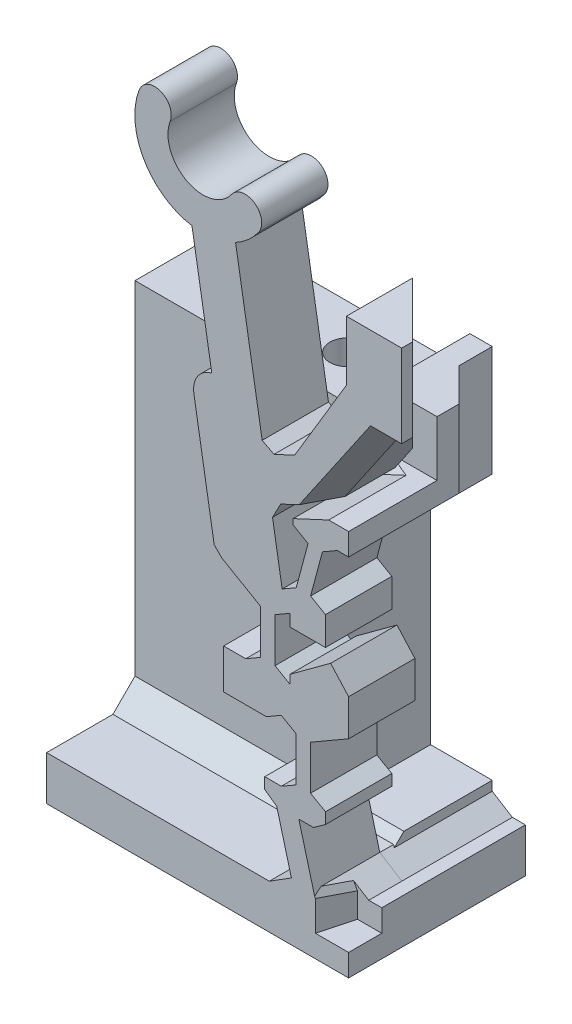
SolidWorks part; units mm, degrees
material "Nylon 6/12"
ref_plane "Front Plane" through (0, 0, 0) normal (0, 0, 1) x (1, 0, 0)
ref_plane "Top Plane" through (0, 0, 0) normal (0, 1, 0) x (1, 0, 0)
ref_plane "Right Plane" through (0, 0, 0) normal (1, 0, 0) x (0, 0, -1)
sketch "Sketch-SkeletonConfigUp" plane through (0, 0, 0) normal (0, 0, 1) x (1, 0, 0)
  line L0 (0, 0) -> (0, -50000) construction
  line L1 (0, 0) -> (4.5811, 6.2164) construction
  line L2 (9.8143, 13.3177) -> (4.5811, 13.945) construction
  line L3 (4.5811, 13.945) -> (2.9713, 10.4094) construction
  line L4 (2.9713, 10.4094) -> (4.5811, 6.2164) construction
  line L5 (4.5811, 13.945) -> (6.2429, 19.1409) construction
  line L6 (2.9713, 10.4094) -> (0.0405, 27.8193) construction
  line L7 (4.5811, 6.2164) -> (9.8143, 13.3177) construction
  line L8 (-587.3593, -797.0242) -> (9.8143, 13.3177) construction
  dimension "D2" = 7.7221
  dimension "D3" = 8.8212
  dimension "D4" = 5.2707
  dimension "D5" = 119.553
  dimension "D6" = 3.8848
  dimension "D7" = 5.4552
  dimension "D8" = 17.6549
  dimension "D9" = 4.4914
  dimension "D10" = 6.745
  dimension "D11" = 145.964
  dimension "D12" = 143.612
sketch "Sketch-SkeletonConfigDown" plane through (0, 0, 0) normal (0, 0, 1) x (1, 0, 0)
  line L0 (0, 0) -> (0, -50000) construction
  line L1 (0, 0) -> (4.5811, 6.2164) construction
  line L2 (9.8143, 13.3177) -> (4.5811, 13.945) construction
  line L3 (4.5811, 13.945) -> (6.1909, 10.4094) construction
  line L4 (6.1909, 10.4094) -> (4.5811, 6.2164) construction
  line L5 (4.5811, 13.945) -> (1.753, 18.6098) construction
  line L6 (6.1909, 10.4094) -> (-8.8652, 19.6294) construction
  line L7 (4.5811, 6.2164) -> (9.8143, 13.3177) construction
  line L8 (-589.9357, -800.5203) -> (9.8143, 13.3177) construction
  dimension "D2" = 7.7221
  dimension "D3" = 8.8212
  dimension "D4" = 5.2707
  dimension "D5" = 119.553
  dimension "D6" = 3.8848
  dimension "D7" = 5.4552
  dimension "D8" = 17.6549
  dimension "D9" = 4.4914
  dimension "D10" = 6.745
  dimension "D11" = 145.964
  dimension "D1" = 143.612
ref_plane "Plane-Cam Base" through (9.128, 0, 0) normal (1, 0, 0) x (0, 0, -1)
ref_plane "Plane-Down-to-Up Derailleur Clearance" through (6.628, 0, 0) normal (1, 0, 0) x (0, 0, -1)
ref_plane "Plane-Cam Cavity Roof" through (5.128, 0, 0) normal (1, 0, 0) x (0, 0, -1)
sketch "Sketch-SwitchBossUp" plane through (0, 0, 0) normal (0, 0, 1) x (1, 0, 0)
  line L0 (3.5811, 11.4759) -> (3.5811, 12.945) construction
  line L2 (6.528, 22.0186) -> (6.528, 24.7229)
  line L3 (6.528, 24.7229) -> (9.028, 24.7229)
  line L5 (5.5811, 12.5552) -> (5.5811, 11.263)
  line L7 (1.5115, 25.1048) -> (2.7157, 17.9518)
  line L8 (-0.4607, 24.7728) -> (0.4359, 19.4465)
  line L9 (2.9713, 10.4094) -> (0.0405, 27.8193) construction
  line L11 (-0.0396, 22.2712) -> (1.9326, 22.6032) construction
  line L15 (6.628, -23.7286) -> (6.628, 23.7286) construction
  line L16 (2.9713, 10.4094) -> (4.5811, 6.2164) construction
  line L17 (3.5811, 12.945) -> (3.5811, 14.945) construction
  line L18 (5.5811, 12.945) -> (5.5811, 14.945) construction
  line L19 (4.2561, 13.945) -> (4.9061, 13.945) construction
  line L20 (3.5811, 14.945) -> (5.5811, 14.945) construction
  line L21 (3.5811, 12.945) -> (5.5811, 12.945) construction
  line L22 (4.5811, 12.945) -> (4.5811, 14.945) construction
  line L23 (4.5811, 6.2164) -> (8.5405, 7.1023) construction
  line L24 (1.9713, 9.4094) -> (1.9713, 11.4094) construction
  line L25 (3.9713, 9.4094) -> (3.9713, 11.4094) construction
  line L26 (3.9713, 9.4094) -> (1.9713, 9.4094) construction
  line L27 (1.9713, 11.4094) -> (3.9713, 11.4094) construction
  line L28 (3.5811, 7.2164) -> (5.5811, 7.2164) construction
  line L29 (3.5811, 7.2164) -> (3.5811, 5.2164) construction
  line L30 (5.5811, 7.2164) -> (5.5811, 5.2164) construction
  line L31 (3.5811, 5.2164) -> (5.5811, 5.2164) construction
  line L32 (4.9061, 6.2164) -> (4.2561, 6.2164) construction
  line L40 (3.2963, 10.4094) -> (2.6463, 10.4094) construction
  line L43 (2.874, 4.5093) -> (0.7934, 4.5093) construction
  line L66 (0.0405, 27.8193) -> (0.0405, 50027.8193) construction
  line L74 (0.5455, 12.7717) -> (-0.3728, 18.2264)
  line L75 (0.3841, 13.7302) -> (2.3564, 14.0622) construction
  line L76 (5.5811, 11.263) -> (5.5811, 12.5552) construction
  line L77 (5.5811, 7.6061) -> (6.628, 8.2105)
  line L80 (5.8152, 10.763) -> (6.628, 9.8603)
  line L81 (9.128, 1033.2419) -> (9.128, 20.0586) construction
  line L82 (2.7987, 17.4587) -> (3.5585, 12.945) construction
  line L83 (3.6203, 12.5779) -> (3.184, 15.1695)
  line L85 (6.9307, 9.5241) -> (8.5405, 7.7363) construction
  line L88 (5.7256, 16.3347) -> (6.8573, 16.3347)
  line L92 (3.7762, 8.3129) -> (6.9307, 9.5241) construction
  line L95 (2.7987, 17.4587) -> (3.101, 15.6625) construction
  line L96 (2.7124, 17.9713) -> (9.128, 19.0513) construction
  line L97 (2.7124, 17.9713) -> (1.7262, 17.8053) construction
  line L98 (1.9713, 9.0197) -> (0.9713, 9.0197)
  line L99 (0.9713, 9.0197) -> (0.9713, 7.2164)
  line L100 (0.9713, 7.2164) -> (2.9061, 7.2164)
  line L101 (4.5811, 6.2164) -> (6.9307, 9.5241) construction
  line L103 (0.0405, 27.8193) -> (1.9448, 26.4638) construction
  line L104 (6.9307, 9.5241) -> (8.5405, 7.7363) construction
  line L106 (13.4904, 14.945) -> (5.5811, 14.945) construction
  line L107 (1.9713, 9.4094) -> (1.9713, 9.0197) construction
  line L109 (0.0405, 27.8193) -> (-2.1498, 28.6358) construction
  line L111 (6.628, 9.8603) -> (6.628, 8.2105)
  line L112 (6.628, 9.8603) -> (6.9307, 9.5241) construction
  line L113 (2.8311, 4.8267) -> (2.8311, 4.3267)
  line L114 (7.3693, 7.7363) -> (7.3563, 7.7363) construction
  line L115 (6.8573, 16.3347) -> (13.4904, 16.3347)
  line L116 (13.4904, 16.3347) -> (13.4904, -1.1653)
  line L117 (13.4904, -1.1653) -> (5.0383, -1.1653)
  line L119 (10.4375, 14.0252) -> (10.4375, 2.1465)
  line L121 (5.0383, -1.1653) -> (5.0383, 1.4614) construction
  line L122 (8.237, 12.8031) -> (10.8637, 12.8031) construction
  line L123 (10.8637, 12.8031) -> (13.4904, 12.8031) construction
  line L124 (10.4375, 2.1465) -> (9.128, 0.837)
  line L125 (8.5892, 7.5847) -> (13.4904, 7.5847) construction
  line L127 (5.5811, 15.3347) -> (5.5811, 14.945) construction
  line L130 (6.0388, 0.837) -> (9.128, 0.837)
  line L132 (2.8311, 4.3267) -> (3.3749, 3.937)
  line L133 (2.9713, 10.4094) -> (6.1909, 10.4094) construction
  line L134 (4.5811, 10.4094) -> (4.5811, 13.945) construction
  line L135 (4.5811, 10.4094) -> (4.5811, 6.2164) construction
  line L136 (0.8973, 12.4192) -> (0.5455, 12.7717)
  line L137 (3.9713, 9.4094) -> (5.5811, 7.2164) construction
  line L139 (5.8152, 10.763) -> (3.9713, 9.4094)
  line L141 (4.0386, 1.4604) -> (3.0388, 0.8347)
  line L142 (3.0388, 0.8347) -> (3.0388, -1.1653)
  line L143 (9.128, 20.0586) -> (9.128, 19.0513) construction
  line L145 (9.128, 18.4729) -> (9.128, -49992.4167) construction
  line L147 (5.5811, 11.263) -> (5.5811, 12.5552) construction
  line L150 (3.0388, -1.1653) -> (5.0383, -1.1653)
  line L151 (3.3749, 3.937) -> (4.3749, 3.937) construction
  line L152 (4.792, 14.945) -> (4.2561, 12.945)
  line L153 (5.442, 14.945) -> (4.9061, 12.945)
  line L157 (3.5811, 16.3347) -> (3.5811, 15.3347) construction
  line L158 (6.117, 15.3347) -> (9.128, 15.3347)
  line L162 (3.2963, 11.4094) -> (3.2963, 9.4094)
  line L164 (2.6463, 11.4094) -> (2.6463, 9.4094)
  line L169 (4.2561, 7.2164) -> (4.2561, 5.2164)
  line L170 (4.9061, 5.2164) -> (4.9061, 7.2164)
  line L175 (4.2561, 7.2164) -> (3.5811, 7.6061)
  line L176 (4.9061, 7.2164) -> (5.5811, 7.6061)
  line L177 (5.5811, 7.2164) -> (5.5811, 7.6061) construction
  line L179 (4.2561, 5.2164) -> (3.5811, 4.8267)
  line L180 (3.5811, 5.2164) -> (3.5811, 4.8267) construction
  line L181 (3.5811, 4.8267) -> (2.8311, 4.8267)
  line L183 (4.9061, 5.2164) -> (5.5811, 4.8267)
  line L184 (5.5811, 5.2164) -> (5.5811, 4.8267) construction
  line L186 (9.128, -23.7286) -> (9.128, 23.7286) construction
  line L187 (2.6463, 9.4094) -> (1.9713, 9.0197)
  line L188 (3.2963, 9.4094) -> (3.9713, 9.0197)
  line L189 (3.2963, 11.4094) -> (3.9713, 11.7991)
  line L190 (2.6463, 11.4094) -> (0.8973, 12.4192)
  line L191 (3.9713, 11.4094) -> (3.9713, 11.7991) construction
  line L192 (3.9713, 11.7991) -> (3.9713, 11.263)
  line L193 (4.9061, 12.945) -> (5.5811, 12.5552)
  line L194 (4.2561, 12.945) -> (3.6203, 12.5779)
  line L195 (3.9713, 11.263) -> (5.5811, 11.263)
  line L196 (3.9713, 9.4094) -> (3.9713, 9.0197)
  line L197 (3.5811, 7.2164) -> (3.5811, 7.6061) construction
  line L199 (3.5811, 7.6061) -> (2.9061, 7.2164)
  line L201 (2.8311, 4.3267) -> (2.8311, 3.937) construction
  line L202 (2.8311, 3.937) -> (3.3749, 3.937) construction
  line L203 (10.4375, 14.0252) -> (9.128, 15.3347)
  line L204 (5.0383, 1.437) -> (3.0388, 1.437) construction
  line L205 (3.0388, 1.437) -> (3.0388, 0.8347) construction
  line L206 (5.0383, 1.4614) -> (6.0388, 0.837)
  line L207 (9.128, 19.0513) -> (9.128, 18.4729) construction
  line L208 (6.628, 17.3072) -> (9.128, 18.4729) construction
  line L209 (9.128, 20.0586) -> (9.128, 18.4729) construction
  line L210 (6.528, 22.0186) -> (4.1882, 18.1066)
  line L211 (5.0383, 1.4614) -> (4.3749, 3.937)
  line L212 (4.0386, 1.4604) -> (3.3749, 3.937)
  line L214 (4.792, 14.945) -> (4.1169, 15.3347)
  line L215 (4.1169, 15.3347) -> (3.5811, 15.3347) construction
  line L216 (5.442, 14.945) -> (6.117, 15.3347)
  line L217 (5.5811, 12.945) -> (5.5811, 12.5552) construction
  line L218 (5.442, 14.945) -> (5.442, 15.3347) construction
  line L219 (6.117, 15.3347) -> (4.1169, 15.3347) construction
  line L221 (9.028, 20.9729) -> (9.028, 24.7229)
  line L223 (4.1169, 15.5846) -> (5.7256, 16.3347)
  line L224 (3.5811, 16.3347) -> (5.7256, 16.3347) construction
  line L225 (3.5542, 15.8738) -> (5.7256, 16.8864)
  line L226 (4.1169, 15.3347) -> (4.1169, 15.5846)
  line L227 (3.5811, 15.3347) -> (4.1169, 15.5846) construction
  line L228 (4.1882, 18.1066) -> (3.2518, 17.67)
  line L229 (9.028, 20.9729) -> (8.528, 20.9729)
  line L230 (8.528, 20.9729) -> (5.7256, 16.8864)
  line L232 (7.5371, 18.7835) -> (9.128, 21.1198) construction
  line L233 (9.128, 21.1198) -> (9.028, 20.9729) construction
  line L234 (6.628, 17.3072) -> (7.5371, 18.7835) construction
  line L236 (5.7256, 16.8864) -> (6.628, 17.3072) construction
  line L237 (3.184, 15.1695) -> (3.5542, 15.8738)
  line L238 (3.2518, 17.67) -> (2.7157, 17.9518)
  line L239 (5.5811, 4.8267) -> (5.5811, 4.3267)
  line L240 (4.3749, 3.937) -> (5.0373, 3.937)
  line L241 (5.0373, 3.937) -> (5.5811, 4.3267)
  arc A0 (1.5115, 25.1048) -> (2.5558, 26.0289) centre (0.0405, 27.8193) ccw
  arc A1 (-0.4607, 24.7728) -> (-2.8525, 28.8978) centre (0.0405, 27.8193) cw
  arc A2 (-2.8525, 28.8978) -> (-1.447, 28.3738) centre (-2.1498, 28.6358) cw
  arc A3 (2.5558, 26.0289) -> (1.3338, 26.8987) centre (1.9448, 26.4638) ccw
  arc A4 (-1.447, 28.3738) -> (1.3338, 26.8987) centre (0.0405, 27.8193) ccw
  arc A5 (3.5811, 12.945) -> (3.5811, 14.945) centre (3.1778, 13.945) ccw construction
  arc A6 (5.5811, 12.945) -> (5.5811, 14.945) centre (5.9843, 13.945) cw construction
  arc A7 (2.5293, 9.921) -> (1.9713, 11.4094) centre (1.568, 10.4094) ccw construction
  arc A8 (3.9713, 11.4094) -> (3.9713, 9.4094) centre (4.3745, 10.4094) ccw construction
  arc A9 (3.5811, 7.2164) -> (3.5811, 5.2164) centre (3.1779, 6.2164) cw construction
  arc A10 (5.5811, 7.2164) -> (5.5811, 5.2164) centre (5.9844, 6.2164) ccw construction
  arc A19 (-0.3728, 18.2264) -> (0.4359, 19.4465) centre (0.6836, 18.4042) cw
  circle A28 centre (0.0405, 27.8193) radius 2.3375 construction
  arc A29 (1.9713, 9.4094) -> (2.5293, 9.921) centre (1.568, 10.4094) ccw construction
  point P53 (4.5811, 13.945)
  point P63 (2.9713, 10.4094)
  point P93 (0.9465, 22.4372)
  point P136 (5.5811, 4.2034)
  dimension "D23" = 1.5875
  dimension "D24" = 0.75
  dimension "D2" = 2
  dimension "D5" = 2
  dimension "D6" = 0.65
  dimension "D8" = 42
  dimension "D14" = 7.5
  dimension "D4" = 3
  dimension "D16" = 42
  dimension "D27" = 120
  dimension "D28" = 120
  dimension "D29" = 120
  dimension "D30" = 120
  dimension "D31" = 120
  dimension "D32" = 120
  dimension "D33" = 120
  dimension "D34" = 120
  dimension "D17" = 0.5
  dimension "D21" = 1
  dimension "D18" = 45
  dimension "D9" = 17.5
  dimension "D22" = 1
  dimension "D15" = 45
  dimension "D38" = 2
  dimension "D39" = 0.5
  dimension "D40" = 60
  dimension "D41" = 1
  dimension "D42" = 45
  dimension "D43" = 120
  dimension "D45" = 2.5
  dimension "D10" = 15
  dimension "D12" = 2.5
  dimension "D13" = 1
  dimension "D19" = 1
  dimension "D25" = 15
  dimension "D26" = 120
  dimension "D35" = 120
  dimension "D37" = 2.5
  dimension "D46" = 25
  dimension "D47" = 3.75
  dimension "D36" = 2.5
  dimension "D44" = 0.5
  dimension "D20" = 3
  dimension "D48" = 2
  dimension "D49" = 0.6
extrude "Boss-Switch Body" add sketch "Sketch-SwitchBossUp" along normal blind 3
sketch "Sketch1" plane through (0, 0, 0) normal (0, 0, -1) x (-1, 0, 0)
  line L1 (-7.5811, -1.1653) -> (0.4122, -1.1653)
  line L2 (-7.5811, -1.1653) -> (-7.5811, 0.837)
  line L4 (0.4122, -1.1653) -> (0.4122, 0.8347)
  line L5 (-4.1169, 18.8347) -> (-7.5811, 18.8347)
  line L10 (-7.5811, 18.8347) -> (-7.5811, 15.3347)
  line L11 (-4.0386, 1.4604) -> (-5.0386, 1.4604)
  line L12 (-7.5811, 15.3347) -> (-4.1169, 15.3347)
  line L13 (-4.0386, 1.4604) -> (-3.0388, 0.8347)
  line L14 (-4.1169, 15.3347) -> (-4.1169, 18.8347)
  line L20 (-4.3749, 3.937) -> (-5.0383, 1.4614) construction
  line L22 (-3.0388, -1.1653) -> (-13.4904, -1.1653) construction
  line L23 (-3.0388, 0.8347) -> (0.4122, 0.8347)
  line L24 (-5.0386, 1.4604) -> (-6.0388, 0.837)
  line L25 (-6.0388, 0.837) -> (-7.5811, 0.837)
  point P5 (-3.5811, 15.3296)
  point P6 (-4.1169, 15.3347)
  point P8 (-4.1169, 18.8347)
  dimension "D1" = 3.5
extrude "Boss-Flange Width" add sketch "Sketch1" along normal blind 5
ref_plane "Plane-Sta2Sit Groove" through (0.0405, 0, 0) normal (1, 0, 0) x (0, 0, -1)
ref_plane "Plane-Cam Outer Surface" through (-12.0395, 0, 0) normal (1, 0, 0) x (0, 0, -1)
ref_plane "Plane-FlangeTop" through (-7.0395, 0, 0) normal (1, 0, 0) x (0, 0, -1)
sketch "Sketch2" plane through (-7.0395, 0, 0) normal (1, 0, 0) x (0, 0, -1)
  line L0 (5, 15.3347) -> (0, 15.3347) construction
  line L1 (5, 17.3347) -> (1, 17.3347)
  line L2 (5, 17.3347) -> (5, 15.3347)
  line L3 (5, 15.3347) -> (1, 15.3347)
  line L4 (1, 17.3347) -> (1, 15.3347)
  line L10 (-3, -1.1653) -> (-3, 16.3347) construction
  line L11 (5, 0.8347) -> (-3, 0.8347)
  line L12 (5, 0.8347) -> (5, -1.1653)
  line L13 (5, -1.1653) -> (-3, -1.1653)
  line L14 (-3, 0.8347) -> (-3, -1.1653)
  line L15 (0, 10.4094) -> (0, 27.8193) construction
  line L17 (5, 0.837) -> (5, -1.1653) construction
  line L18 (-3, 0.8347) -> (0, 0.8347) construction
  dimension "D1" = 1
  dimension "D2" = 2
extrude "Boss-Flange Height" add sketch "Sketch2" along normal up to surface (11.6675 mm away)
sketch "Sketch10" plane through (0, 15.3347, 0) normal (0, 1, 0) x (1, 0, 0)
  line L0 (9.128, -23.7286) -> (9.128, 23.7286) construction
  line L1 (7.5811, 5) -> (5.128, 5)
  line L2 (7.5811, 5) -> (7.5811, 2)
  line L3 (7.5811, 2) -> (5.128, 2)
  line L5 (4.628, 7) -> (4.628, 1) construction
  line L6 (4.1169, 1) -> (-7.0395, 1) construction
  line L8 (5.128, 5) -> (5.128, 2)
  dimension "D1" = 1
  dimension "D2" = 0.5
  dimension "D3" = 4.5
extrude "Cut-Up-To-Down Derailleur Clearance" cut sketch "Sketch10" along normal up to next
sketch "Sketch17" plane through (0, 15.3347, 0) normal (0, -1, 0) x (1, 0, 0)
  line L0 (5.128, -5) -> (-7.0395, -5)
  line L1 (5.128, -5) -> (-7.0395, -5) construction
  line L2 (-7.0395, -5) -> (-7.0395, -1)
  line L3 (-7.0395, -1) -> (5.128, -1)
  line L4 (5.128, -1) -> (5.128, -5)
  line L5 (-7.0395, -1) -> (-7.0395, -5) construction
extrude "Boss-Flange Support" add sketch "Sketch17" along normal up to surface (14.5 mm away) up to face at (-2.0003, 0.8347, -1)
sketch "Sketch-HolePositions" plane through (0, -1.1653, 0) normal (0, -1, 0) x (1, 0, 0)
  line L0 (-7.0395, -3) -> (7.5811, -3) construction
  line L1 (7.5811, -5) -> (-7.0395, -5) construction
  line L2 (7.5811, -5) -> (7.5811, 0) construction
  line L4 (-7.0395, -22.2167) -> (-7.0395, 22.2167) construction
  point P6 (-4.0395, -3)
  point P7 (0.5811, -3)
  dimension "D1" = 3
  dimension "D2" = 4.6206
  dimension "D3" = 2
sketch "Sketch6" plane through (0, -1.1653, 0) normal (0, -1, 0) x (-1, 0, 0)
  point P0 (4.0395, 3)
  point P3 (-0.5811, 3)
hole_wizard "Tap Drill for M2x0.4 Tap1" positions "Sketch6" profile "Sketch5" hole size "M2x0.4" standard "ANSI Metric" end condition through all
sketch "Sketch5" plane through (-4.0395, -1.1653, -3) normal (1, 0, 0) x (0, 0, -1)
  line L0 (0, 0) -> (0, 30.5511)
  line L1 (0, 30.5511) -> (0.8, 30.5511)
  line L2 (0.8, 30.5511) -> (0.8, 0)
  line L5 (0.8, 0) -> (0, 0)
  line L11 (0, -6.35) -> (0, 107.95) construction
  dimension "Thru Hole Dia." = 1.6
  dimension "Thru Hole Depth" = 30.5511
sketch "Sketch9" plane through (0, -1.1653, 0) normal (0, -1, 0) x (1, 0, 0)
  point P0 (-4.0395, -3)
  point P3 (0.5811, -3)
hole_wizard "M2 Clearance Hole2" positions "Sketch9" profile "Sketch8" hole size "M2" standard "ANSI Metric"
sketch "Sketch8" plane through (-4.0395, -1.1653, -3) normal (1, 0, 0) x (0, 0, -1)
  line L0 (0, 0) -> (0, 15.721)
  line L1 (0, 15.721) -> (1.2, 15)
  line L2 (1.2, 15) -> (1.2, 0)
  line L5 (1.2, 0) -> (0, 0)
  line L10 (0, 15.721) -> (-1.2, 15) construction
  line L11 (0, -6.35) -> (0, 107.95) construction
  dimension "Hole Dia." = 2.4
  dimension "Hole Depth" = 15
  dimension "Drill Angle" = 118
sketch "Sketch-Measurements for Derailleur Ramps" plane through (0, 0, 0) normal (0, 0, 1) x (1, 0, 0)
  line L0 (3.184, 15.1695) -> (2.4687, 19.4188)
  line L1 (2.8264, 17.2941) -> (1.8402, 17.1281)
  line L2 (2.9713, 10.4094) -> (0.0405, 27.8193) construction
  line L3 (1.8402, 17.1281) -> (-1.3081, 15.0016)
  line L4 (6.1909, 10.4094) -> (-8.8652, 19.6294) construction
  line L5 (1.8402, 17.1281) -> (2.6012, 12.6077)
  line L6 (2.6012, 12.6077) -> (-1.3081, 15.0016)
  line L7 (0.2661, 16.0649) -> (0.2661, 17.1281)
  line L8 (0.2661, 17.1281) -> (1.8402, 17.1281)
  line L9 (6.1909, 10.4094) -> (2.9713, 10.4094)
  line L10 (5.386, 8.3129) -> (3.7762, 8.3129)
  line L11 (2.7157, 17.9518) -> (1.5115, 25.1048) construction
  line L12 (6.1909, 10.4094) -> (4.5811, 6.2164) construction
  line L13 (4.5811, 8.3129) -> (4.5811, 8.7912)
  line L14 (4.5811, 6.2164) -> (5.386, 8.3129)
  line L15 (2.9713, 10.4094) -> (4.5811, 6.2164) construction
  line L16 (3.7762, 8.3129) -> (4.5811, 6.2164)
  line L17 (5.386, 8.3129) -> (5.386, 8.7912)
  point P18 (0, 0)
  point P30 (3.101, 15.6625)
  point P31 (3.184, 15.1695)
  point P33 (2.4687, 19.4188)
  dimension "D1" = 1.5742
  dimension "D2" = 0.8049
sketch "Sketch12" plane through (0, 24.7229, 0) normal (0, 1, 0) x (1, 0, 0)
  line L0 (6.528, 0) -> (9.028, -2.5)
  line L1 (9.028, -2.5) -> (9.028, 0)
  line L2 (9.028, 0) -> (6.528, 0)
  line L5 (9.028, -3) -> (9.028, 0) construction
  point P8 (8.7264, -2.1984)
  point P9 (9.028, -2.4968)
  point P10 (9.028, -2.4838)
  dimension "D1" = 45
extrude "Cut-Up-to-Down Cantilever Slope" cut sketch "Sketch12" against normal up to next
ref_plane "Plane1" through (0, 7.1023, 0) normal (0, 1, 0) x (1, 0, 0)
sketch "Sketch-Derailleur Location" plane through (0, 7.1023, 0) normal (0, 1, 0) x (1, 0, 0)
  line L0 (9.028, 0) -> (9.028, -3)
  line L1 (4.0386, -3) -> (3.0388, -3) construction
  line L2 (-119237.4187, 0) -> (9.8143, 0) construction
  point P0 (9.028, 0)
  point P1 (0, 0)
  point P8 (9.028, -1.5)
ref_plane "Plane-Cantilever Cut" [suppressed] through (7.0848, 8.5204, -1.9058) normal (-0.6301, -0.7578, 0.1695) x (-0.7765, 0.6151, -0.1368)
sketch "Sketch14" [suppressed] plane through (7.0848, 8.5204, -1.9058) normal (-0.6301, -0.7578, 0.1695) x (-0.7765, 0.6151, -0.1368)
  line L0 (2.3023, -1.6911) -> (-0.3551, -1.6911)
  line L2 (2.3023, -4.3362) -> (2.3023, -1.6911)
  line L3 (-0.3551, -1.6911) -> (-0.3551, -4.4608)
  line L5 (-0.3551, -4.4608) -> (1.0087, -5.0843)
  line L6 (1.0087, -5.0843) -> (2.3023, -4.3362)
extrude "Cut-Down-to-Up Cantilever Slope" [suppressed] cut sketch "Sketch14" against normal up to next
sketch "Sketch16" plane through (0, 0, 0) normal (0, 0, -1) x (-1, 0, 0)
  line L0 (-7.5811, 18.8347) -> (-13.4904, 18.8347)
  line L1 (-13.4904, 18.8347) -> (-13.4904, -1.1653)
  line L2 (-13.4904, -1.1653) -> (-6.628, -1.1653)
  line L3 (-13.4904, -1.1653) -> (-5.0383, -1.1653) construction
  line L4 (-6.628, -1.1653) -> (-6.628, 5.2038)
  line L5 (-6.628, 5.2038) -> (-8.0037, 5.2038)
  line L6 (-8.0037, 5.2038) -> (-8.0037, 12.0484)
  line L7 (-8.0037, 12.0484) -> (-6.628, 12.0484)
  line L8 (-6.628, 12.0484) -> (-6.628, 17.6306)
  line L9 (-6.628, 23.7286) -> (-6.628, -23.7286) construction
  line L10 (-4.6236, 18.8347) -> (-6.528, 18.8347) construction
  line L11 (-7.5811, 18.8347) -> (-6.628, 17.6306)
  point P0 (-6.628, 17.6306)
extrude "Cut-Down-to-Up Derailleur Clearance" cut sketch "Sketch16" against normal through all and the other way through all
ref_plane "Plane-Symmetry Plane" through (0, 0, 1.5) normal (0, 0, 1) x (1, 0, 0)
sketch "Sketch-Cable Center Point" plane through (0, 0, 1.5) normal (0, 0, 1) x (1, 0, 0)
  line L0 (0.0405, 27.8193) -> (0.1722, 27.0366)
  line L1 (2.9713, 10.4094) -> (0.0405, 27.8193) construction
  point P0 (0.0405, 27.8193)
  dimension "D1" = 0.7937
chamfer "Chamfer-Flange Support" distance 1.5 angle 45 1 edges at (4.1169, 17.3347, -3)
chamfer "Chamfer-Flange Support 2" distance 1.5 angle 45 2 edges at (5.128, 17.0847, -2) (5.128, 15.3347, -1.5)
chamfer "Chamfer-Flange Support 3" distance 1 angle 45 1 edges at (-2.0003, 0.8347, -1)
sketch "Sketch18" plane through (6.628, 0, 0) normal (1, 0, 0) x (0, 0, -1)
  line L1 (-3, -0.163) -> (-1.5, -0.163)
  line L2 (-3, -0.163) -> (-3, 1.4604)
  line L3 (-3, 1.4604) -> (-1.5, 1.4604)
  line L4 (-1.5, -0.163) -> (-1.5, 1.4604)
  line L5 (0.6257, 1.4604) -> (0, 1.4604) construction
  line L6 (-3, -1.1653) -> (-3, 0.837) construction
  line L7 (-3, 0.837) -> (0, 0.837) construction
  dimension "D1" = 1.5
  dimension "D2" = 1
extrude "Cut-Down-to-Up Derailleur Clearance 2" cut sketch "Sketch18" against normal blind 1
sketch "Sketch19" plane through (0, 0, 0) normal (0, 0, 1) x (1, 0, 0)
  line L1 (4.1169, 16.1363) -> (4.1169, 18.0734) construction
  line L5 (4.1169, 18.0734) -> (4.1169, 18.8347) construction
  line L7 (4.1169, 18.8347) -> (6.628, 18.8347)
  line L8 (6.628, 18.8347) -> (6.628, 16.3347)
  line L10 (4.1169, 15.5846) -> (4.1169, 18.8347)
  line L11 (6.628, 16.3347) -> (6.628, 17.6306) construction
  line L12 (4.1169, 18.8347) -> (4.6236, 18.8347) construction
  line L14 (4.1169, 15.5846) -> (4.1169, 16.1363) construction
  line L15 (6.628, -23.7286) -> (6.628, 23.7286) construction
  line L16 (6.628, 15.3347) -> (6.628, 16.3347) construction
  line L17 (6.628, 16.3347) -> (5.7256, 16.3347)
  line L18 (5.7256, 16.3347) -> (4.1169, 15.5846)
extrude "Cut-Up-to-Down Cantilever Clearance" cut sketch "Sketch19" against normal up to surface (1 mm away) up to face at (1.707, 12.7097, -1)
chamfer "Chamfer3" distance 0.3 angle 60 1 edges at (4.1169, 15.4596, -1) first distance on face at (4.1169, 15.4346, 0.8)
chamfer "Chamfer4" distance 0.5 angle 60 1 edges at (5.1126, 15.3347, -1) first distance on face at (5.3316, 15.3347, 0.4714)
chamfer "Chamfer7" [suppressed] distance 1 angle 45
sketch "Sketch22" plane through (0, 0, 0) normal (0, 0, 1) x (1, 0, 0)
  line L0 (6.628, 17.6306) -> (7.5811, 18.8347) construction
  line L1 (6.628, 18.8347) -> (7.5811, 18.8347) construction
  line L2 (6.628, 17.6306) -> (6.628, 18.8347) construction
  line L3 (6.628, 17.6306) -> (7.5811, 18.8347)
  line L4 (6.628, 18.8347) -> (7.5811, 18.8347)
  line L5 (6.628, 17.6306) -> (6.628, 18.8347)
extrude "Cut-Extrude3" cut sketch "Sketch22" against normal up to next
sketch "Sketch23" plane through (0, 0, -1) normal (0, 0, 1) x (1, 0, 0)
  line L0 (5.128, 1.8347) -> (2.3369, 1.8347)
  line L1 (-7.0395, 1.8347) -> (5.128, 1.8347) construction
  line L2 (2.3369, 1.8347) -> (2.3369, 13.8347)
  line L3 (2.3369, 13.8347) -> (5.128, 13.8347)
  line L4 (5.128, 13.8347) -> (5.128, 1.8347)
extrude "Cut-Extrude4" cut sketch "Sketch23" against normal through all
chamfer "Chamfer9" distance 0.5 angle 45 1 edges at (4.6614, 15.8385, -1)
chamfer "Chamfer10" distance 0.75 angle 45 1 edges at (7.1268, 18.9297, 3)
chamfer "Chamfer11" distance 0.5 angle 75 1 edges at (5.628, 0.4652, 3) first distance on face at (3.6601, 11.8074, 3)
chamfer "Chamfer12" distance 0.2 angle 30 1 edges at (5.3289, 1.28, 2.25) first distance on face at (5.3289, 0.5585, 2.25)
equation "\"axle-diameter\"=2"
equation "\"switch-thickness\"=12"
equation "\"base-width\"=4.0"
equation "\"axle-bushing-radius\"=3"
equation "\"clearance\"= 0.25"
equation "\"arm-width\"=1.5"
equation "\"min-diameter\"=70"
equation "\"alpha\"=143.6120"
equation "\"gamma\"=119.5526"
equation "\"delta\"=145.9637"
equation "\"epsilon\"=6.7452"
equation "\"l_AB\"=8.8212"
equation "\"l_AC\"=4.4914"
equation "\"l_BD\"=5.2707"
equation "\"l_CD\"=3.8848"
equation "\"l_CE\"=17.6549"
equation "\"l_DF\"=5.4552"
equation "\"l_OA\"=7.7221"
equation "\"D2@Sketch-SkeletonConfigUp\" = \"l_OA\""
equation "\"D3@Sketch-SkeletonConfigUp\" = \"l_AB\""
equation "\"D4@Sketch-SkeletonConfigUp\" = \"l_BD\""
equation "\"D5@Sketch-SkeletonConfigUp\" = \"gamma\""
equation "\"D6@Sketch-SkeletonConfigUp\" = \"l_CD\""
equation "\"D7@Sketch-SkeletonConfigUp\" = \"l_DF\""
equation "\"D8@Sketch-SkeletonConfigUp\" = \"l_CE\""
equation "\"D9@Sketch-SkeletonConfigUp\" = \"l_AC\""
equation "\"D_groove\"=3.175"
equation "\"D7@Sketch-SkeletonConfigDown\" = \"l_DF\""
equation "\"D6@Sketch-SkeletonConfigDown\" = \"l_CD\""
equation "\"D2@Sketch-SkeletonConfigDown\" = \"l_OA\""
equation "\"D3@Sketch-SkeletonConfigDown\" = \"l_AB\""
equation "\"D9@Sketch-SkeletonConfigDown\" = \"l_AC\""
equation "\"D8@Sketch-SkeletonConfigDown\" = \"l_CE\""
equation "\"D5@Sketch-SkeletonConfigDown\" = \"gamma\""
equation "\"D4@Sketch-SkeletonConfigDown\" = \"l_BD\""
equation "\"D1@Sketch-SkeletonConfigDown\" = \"alpha\""
equation "\"hinge_length\"=1.5"
equation "\"hinge_depth\"=0.25"
equation "\"D10@Sketch-SkeletonConfigUp\"=\"epsilon\""
equation "\"D11@Sketch-SkeletonConfigUp\"=\"delta\""
equation "\"D12@Sketch-SkeletonConfigUp\"=\"alpha\""
equation "\"D11@Sketch-SkeletonConfigDown\"=\"delta\""
equation "\"D10@Sketch-SkeletonConfigDown\"=\"epsilon\""
equation "\"EE_dx\"=8.9056"
equation "\"EE_dy\"=8.1898"
equation "\"r_groove\"=\"D_groove\"/2"
equation "\"t_wall\"=25.4/16"
equation "\"width_lower\"=\"D_groove\"+\"t_wall\""
equation "\"cable_to_bottom\"=30.6257"
equation "\"switch_EE-up_base_dy\"=24"
equation "\"switch_EE-down_base_dy\"=16"
equation "\"D_axle\"=25.4/8"
equation "\"D_up_to_down\"=16"
equation "\"D_down_to_up\"=25"
equation "\"t_cam_base\"=7.5"
equation "\"D23@Sketch-SwitchBossUp\"=\"D_groove\"/2"
equation "\"D1@Sketch-Cable Center Point\"=\"D_groove\"/4"
